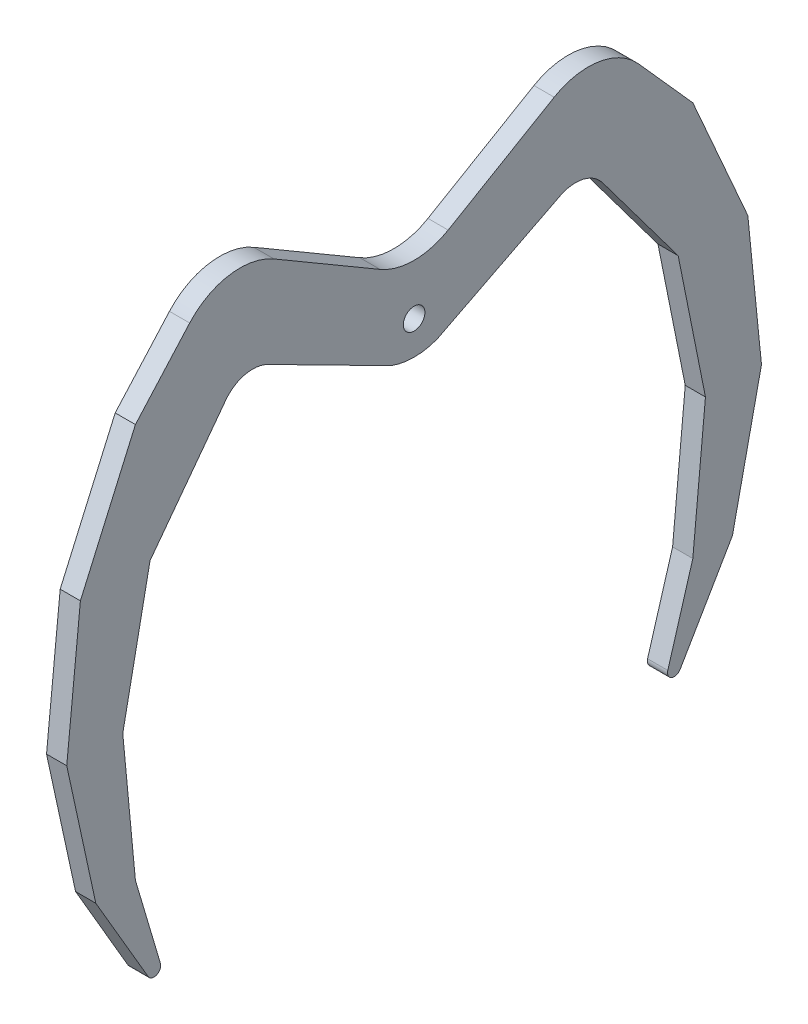
SolidWorks part; units mm, degrees
ref_plane "Front Plane" through (0, 0, 0) normal (0, 0, 1) x (1, 0, 0)
ref_plane "Top Plane" through (0, 0, 0) normal (0, 1, 0) x (1, 0, 0)
ref_plane "Right Plane" through (0, 0, 0) normal (1, 0, 0) x (0, 0, -1)
sketch "Sketch1" plane through (0, 0, 0) normal (1, 0, 0) x (0, 0, -1)
  line L0 (7, 16.8692) -> (7, -36.1211) construction
  line L2 (27.7808, 17.0667) -> (12.0517, 7.8596)
  line L3 (10.4202, -5.3219) -> (28.6824, 3.9599)
  line L4 (48.344, -52.4862) -> (44.6332, -65.004)
  line L5 (-20.846, 1.2022) -> (-20.846, 21.2022) construction
  line L7 (-26.2953, 15.0929) -> (-34.344, 6.0692)
  line L8 (-34.344, 6.0692) -> (-42.505, -12.4943)
  line L9 (-42.505, -12.4943) -> (-44.5302, -32.6711)
  line L10 (-44.5302, -32.6711) -> (-40.2213, -52.4862)
  line L11 (-40.2213, -52.4862) -> (-32.4557, -65.7923)
  line L12 (-32.172, -12.4943) -> (-36.2203, -32.6711)
  line L13 (-36.2203, -32.6711) -> (-34.344, -52.4862)
  line L14 (-34.344, -52.4862) -> (-30.6332, -65.004)
  line L15 (0, -6) -> (0, 9) construction
  line L16 (-13.7808, 17.0667) -> (1.9483, 7.8596)
  line L18 (50.2203, -32.6711) -> (48.344, -52.4862)
  line L19 (46.172, -12.4943) -> (50.2203, -32.6711)
  line L20 (54.2213, -52.4862) -> (46.4557, -65.7923)
  line L21 (58.5302, -32.6711) -> (54.2213, -52.4862)
  line L22 (56.505, -12.4943) -> (58.5302, -32.6711)
  line L23 (48.344, 6.0692) -> (56.505, -12.4943)
  line L24 (40.2953, 15.0929) -> (48.344, 6.0692)
  line L26 (34.9509, 2.4986) -> (46.172, -12.4943)
  line L27 (-12.0891, 26.3129) -> (-20.846, 21.2022) [skipped]
  line L28 (16.4829, 35.7324) -> (6.5753, 33.578) [skipped]
  line L29 (36.6597, 33.7073) -> (26.5713, 34.7199) [skipped]
  line L30 (55.2232, 25.5463) -> (45.9415, 29.6268) [skipped]
  line L31 (70.3563, 12.0482) -> (62.7898, 18.7972) [skipped]
  line L32 (80.5775, -5.4655) -> (75.4669, 3.2913) [skipped]
  line L33 (67.9513, -71.5875) -> (74.7003, -64.021) [skipped]
  line L34 (84.8865, -25.2807) -> (82.732, -15.3731) [skipped]
  line L35 (83.8739, -35.3691) -> (84.8865, -25.2807) [skipped]
  line L36 (74.7003, -64.021) -> (78.7808, -54.7392) [skipped]
  line L37 (52.4454, -84.2647) -> (61.2022, -79.154) [skipped]
  line L38 (33.7809, -91.5298) -> (43.6885, -89.3753) [skipped]
  line L39 (13.785, -92.6716) -> (23.8734, -93.6842) [skipped]
  line L40 (-14.867, -83.498) -> (-5.5852, -87.5785) [skipped]
  line L41 (-30, -70) -> (-22.4335, -76.749) [skipped]
  line L42 (3.5798, -5.3219) -> (-14.6824, 3.9599)
  line L43 (-20.9509, 2.4986) -> (-32.172, -12.4943)
  circle A0 centre (7, -0.9896) radius 1.6
  arc A1 (27.7808, 17.0667) -> (40.2953, 15.0929) centre (32.8326, 8.4365) cw
  arc A2 (-26.2953, 15.0929) -> (-13.7808, 17.0667) centre (-18.8326, 8.4365) cw
  arc A3 (28.6824, 3.9599) -> (34.9509, 2.4986) centre (30.9479, -0.4974) cw
  arc A4 (-14.6824, 3.9599) -> (-20.9509, 2.4986) centre (-16.9479, -0.4974) ccw
  arc A6 (1.9483, 7.8596) -> (12.0517, 7.8596) centre (7, 16.4898) ccw
  arc A7 (44.6332, -65.004) -> (46.4557, -65.7923) centre (45.592, -65.2882) ccw
  arc A8 (-30.6332, -65.004) -> (-32.4557, -65.7923) centre (-31.592, -65.2882) cw
  arc A9 (3.5798, -5.3219) -> (10.4202, -5.3219) centre (7, 3.6174) ccw
  point P33 (34.846, 21.2022)
  point P75 (7, -8.9329)
  point P78 (7, 4.9025)
  point P80 (42.2771, -72.9521)
  point P83 (-28.2771, -72.9521)
  dimension "D1" = 7
  dimension "D2" = 10
  dimension "D3" = 5
  dimension "D5" = 1
extrude "Boss-Extrude1" add sketch "Sketch1" along normal blind 3
